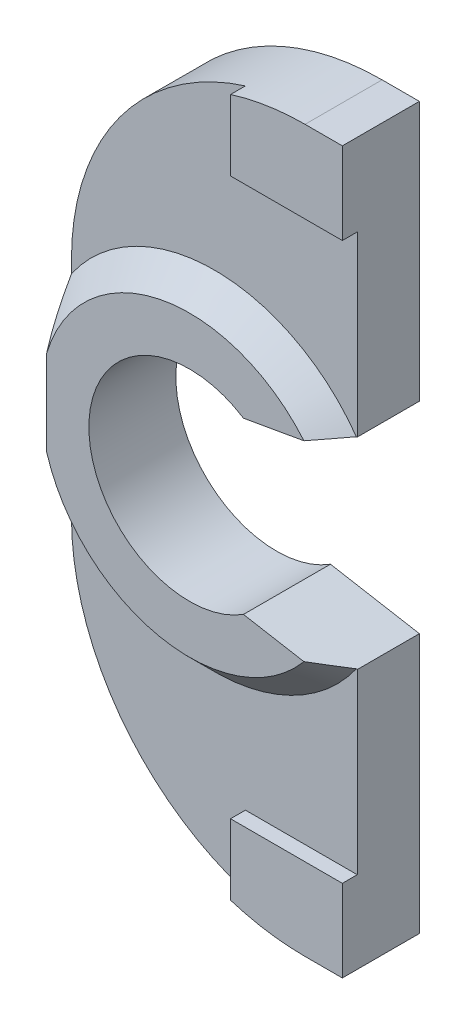
SolidWorks part; units mm, degrees
ref_plane "Front Plane" through (0, 0, 0) normal (0, 0, 1) x (1, 0, 0)
ref_plane "Top Plane" through (0, 0, 0) normal (0, 1, 0) x (1, 0, 0)
ref_plane "Right Plane" through (0, 0, 0) normal (1, 0, 0) x (0, 0, -1)
sketch "Sketch2" plane through (0, 0, 0) normal (0, 0, 1) x (1, 0, 0)
  line L1 (5.75, -14.5) -> (4.25, -14.5)
  line L2 (5.75, -14.5) -> (5.75, -4.05)
  line L3 (5.75, 14.5) -> (4.25, 14.5)
  line L4 (-5.75, -4.5) -> (-5.75, 4.5)
  line L5 (5.75, -14.5) -> (1.4929, -3.7648) construction
  line L6 (5.75, 14.5) -> (1.606, 4.05) construction
  line L8 (5.75, 4.05) -> (5.75, 14.5)
  line L9 (0, 0) -> (-5.75, -14.5) construction
  line L10 (-1.4929, 3.7648) -> (-5.75, 14.5) construction
  line L11 (5.75, 4.05) -> (2.171, 3.4189)
  line L12 (5.75, -4.05) -> (2.171, -3.4189)
  arc A1 (4.25, -14.5) -> (-5.75, -4.5) centre (4.25, -4.5) cw
  arc A2 (-5.75, 4.5) -> (4.25, 14.5) centre (4.25, 4.5) cw
  arc A3 (2.171, 3.4189) -> (2.171, -3.4189) centre (0, 0) ccw
  point P0 (0, 0)
  dimension "D4" = 10
  dimension "D1" = 11.5
  dimension "D2" = 29
extrude "Boss-Extrude1" add sketch "Sketch2" along normal blind 2.5
sketch "Sketch3" plane through (0, 0, 2.5) normal (0, 0, 1) x (1, 0, 0)
  line L4 (-5.75, 4.5) -> (-5.75, -4.5) construction
  line L5 (-5.75, 1.7139) -> (-5.75, -1.7139)
  line L6 (2.171, 3.4189) -> (5.75, 4.05) construction
  line L7 (5.75, -4.05) -> (2.171, -3.4189) construction
  line L8 (2.171, 3.4189) -> (4.6037, 3.8479)
  line L9 (4.6037, -3.8479) -> (2.171, -3.4189)
  arc A1 (0, 4.05) -> (0, -4.05) centre (0, 0) ccw
  arc A2 (4.6037, 3.8479) -> (-5.75, 1.7139) centre (0, 0) ccw
  arc A3 (-5.75, -1.7139) -> (4.6037, -3.8479) centre (0, 0) ccw
  arc A4 (2.171, 3.4189) -> (2.171, -3.4189) centre (0, 0) ccw construction
  arc A5 (2.171, 3.4189) -> (2.171, -3.4189) centre (0, 0) ccw
  line M8 (-5.75, 4.5) -> (-5.75, -4.5)
  line M17 (5.75, -4.05) -> (2.171, -3.4189)
  arc M18 (2.171, -3.4189) -> (2.171, 3.4189) centre (0, 0) cw
  line M19 (2.171, 3.4189) -> (5.75, 4.05)
  dimension "D1" = 12
extrude "Boss-Extrude2" add sketch "Sketch3" along normal blind 1 contours A3 A2 M8 M17 M18 M19
sketch "Sketch4" plane through (0, 0, 2.5) normal (0, 0, 1) x (1, 0, 0)
  line L0 (5.75, 11.2) -> (1.25, 11.2)
  line L1 (1.25, 11.2) -> (1.25, 14.0394)
  line L5 (5.75, 4.05) -> (5.75, 14.5)
  line L6 (5.75, 14.5) -> (4.25, 14.5)
  line L7 (-5.75, 4.5) -> (-5.75, 1.7139)
  line L9 (5.75, 4.05) -> (5.75, 14.5)
  line L10 (5.75, 14.5) -> (4.25, 14.5)
  line L11 (-5.75, 4.5) -> (-5.75, 1.7139)
  line L15 (4.6037, 3.8479) -> (5.75, 4.05)
  line L16 (4.6037, 3.8479) -> (5.75, 4.05)
  arc A2 (4.6037, 3.8479) -> (-5.75, 1.7139) centre (0, 0) ccw
  arc A3 (4.25, 14.5) -> (-5.75, 4.5) centre (4.25, 4.5) ccw
  arc A4 (4.6037, 3.8479) -> (-5.75, 1.7139) centre (0, 0) ccw
  arc A5 (4.25, 14.5) -> (-5.75, 4.5) centre (4.25, 4.5) ccw
  line M9 (5.75, 4.05) -> (5.75, 14.5)
  line M10 (5.75, 14.5) -> (4.25, 14.5)
  arc M11 (4.25, 14.5) -> (-5.75, 4.5) centre (4.25, 4.5) ccw
  dimension "D2" = 4.5
  dimension "D3" = 3.3
  dimension "D1" = 0
extrude "Boss-Extrude3" add sketch "Sketch4" along normal blind 0.6 contours L1 L0 M9 M10 M11
mirror "Mirror1" about plane through (0, 0, 0) normal (0, 1, 0) of "Boss-Extrude3"
chamfer "Chamfer2" distance 1 angle 45 2 edges
